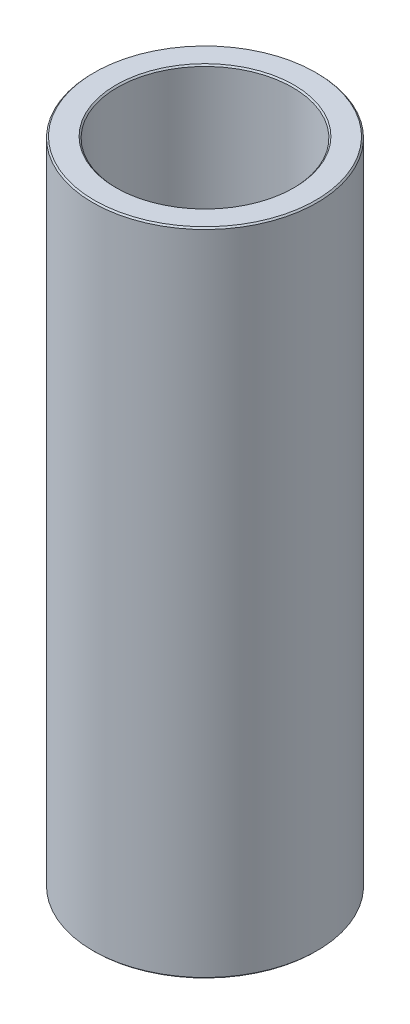
SolidWorks part; units mm, degrees
ref_plane "Front Plane" through (0, 0, 0) normal (0, 0, 1) x (1, 0, 0)
ref_plane "Top Plane" through (0, 0, 0) normal (0, 1, 0) x (1, 0, 0)
ref_plane "Right Plane" through (0, 0, 0) normal (1, 0, 0) x (0, 0, -1)
sketch "Sketch1" plane through (0, 0, 0) normal (0, 1, 0) x (1, 0, 0)
  circle A0 centre (0, 0) radius 35
  dimension "SLEEVE_OD" = 70
extrude "Boss-Extrude1" add sketch "Sketch1" along normal blind 203.106
sketch "Sketch2" plane through (0, 0, 0) normal (0, 1, 0) x (1, 0, 0)
  circle A0 centre (0, 0) radius 27.3615
  dimension "BORE_D" = 54.723
extrude "Cut-Extrude1" cut sketch "Sketch2" along normal through all
chamfer "Chamfer1" distance 0.4412 angle 45 4 edges at (0, 203.106, 27.3615) (0, 0, 27.3615) (0, 0, 35) (0, 203.106, 35)
